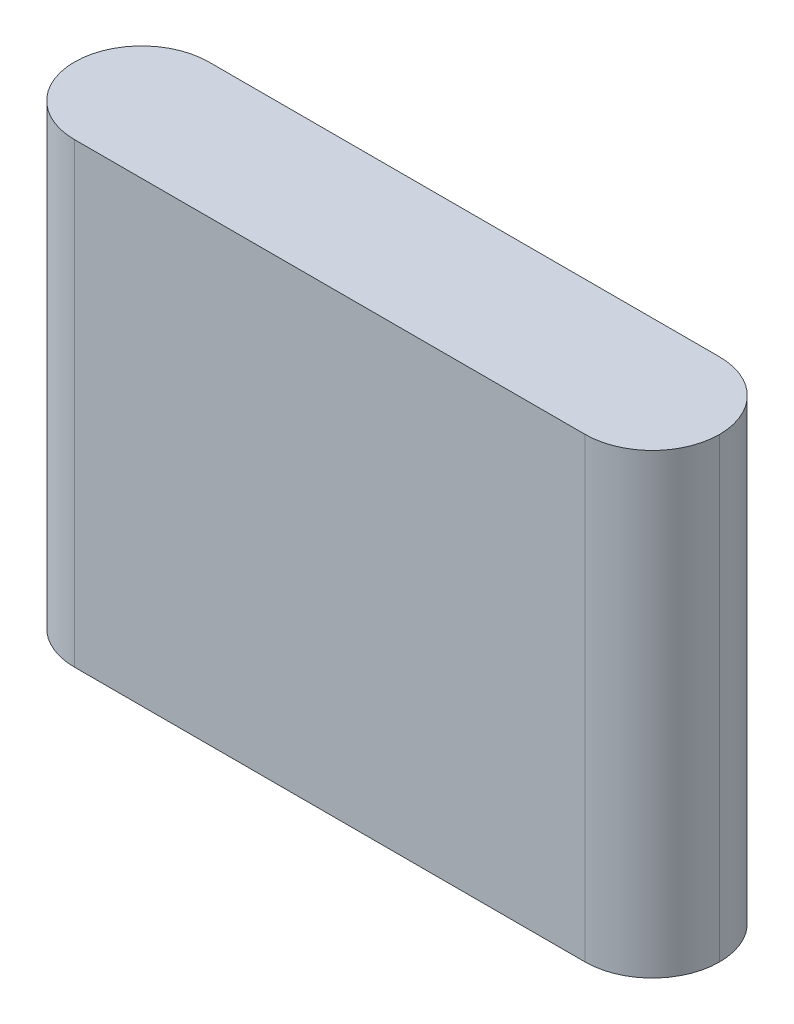
SolidWorks part; units mm, degrees
ref_plane "Front" through (0, 0, 0) normal (0, 0, 1) x (1, 0, 0)
ref_plane "Top" through (0, 0, 0) normal (0, 1, 0) x (1, 0, 0)
ref_plane "Right" through (0, 0, 0) normal (1, 0, 0) x (0, 0, -1)
sketch "Sketch1" plane through (0, 0, 0) normal (0, 0, 1) x (1, 0, 0)
  line L1 (-36, 25.5) -> (36, 25.5)
  line L2 (-36, 25.5) -> (-36, -25.5)
  line L3 (-36, -25.5) -> (36, -25.5)
  line L4 (36, 25.5) -> (36, -25.5)
  line L5 (-36, 25.5) -> (36, -25.5) construction
  line L6 (-36, -25.5) -> (36, 25.5) construction
  point P0 (0, 0)
  dimension "D1" = 72
  dimension "D2" = 51
extrude "Boss-Extrude1" add sketch "Sketch1" along normal blind 15
fillet "Fillet2" radius 7.5 1 edges at (36, 0, 15)
fillet "Fillet3" radius 7.5 3 edges at (-36, 0, 15) (-36, 0, 0) (36, 0, 0)
